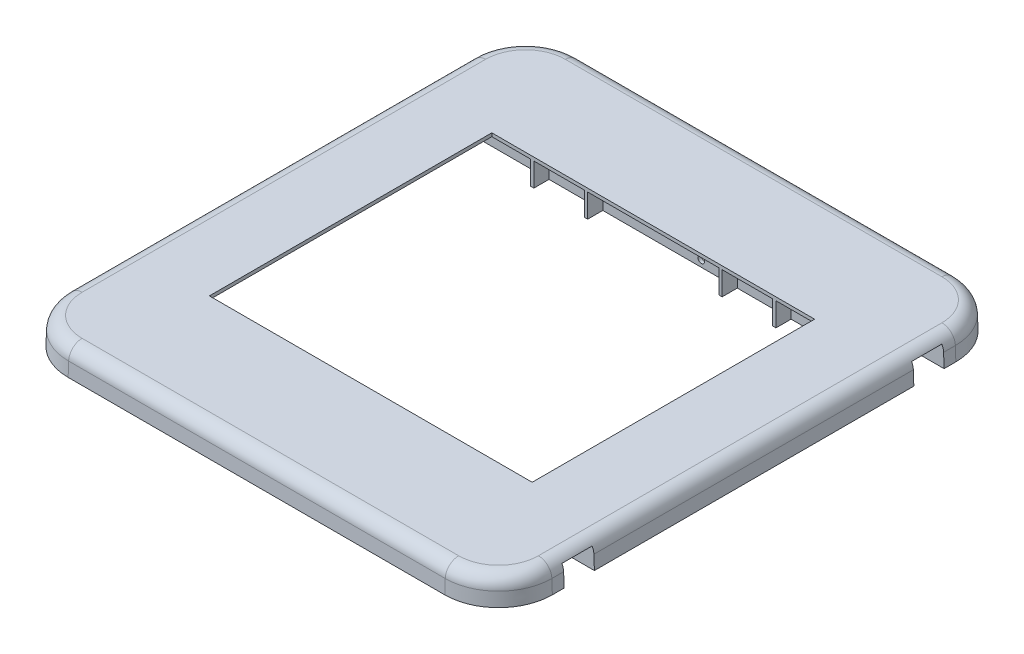
SolidWorks part; units mm, degrees
material "ABS PC"
ref_plane "Front Plane" through (0, 0, 0) normal (0, 0, 1) x (1, 0, 0)
ref_plane "Top Plane" through (0, 0, 0) normal (0, 1, 0) x (1, 0, 0)
ref_plane "Right Plane" through (0, 0, 0) normal (1, 0, 0) x (0, 0, -1)
sketch "Sketch1" plane through (0, 0, 0) normal (0, 1, 0) x (1, 0, 0)
  line L1 (-228.6, 0) -> (-256.2277, 0) construction
  line L2 (228.6, 0) -> (228.6, 190.5)
  line L3 (177.8, 241.3) -> (-177.8, 241.3)
  line L4 (-228.6, 0) -> (-228.6, 190.5)
  line L5 (-228.6, 0) -> (228.6, 0)
  arc A0 (-177.8, 241.3) -> (-228.6, 190.5) centre (-177.8, 190.5) ccw
  arc A1 (228.6, 190.5) -> (177.8, 241.3) centre (177.8, 190.5) ccw
  dimension "D3" = 50.8
  dimension "D1" = 457.2
  dimension "D2" = 482.6
extrude "Extrude1" add sketch "Sketch1" along normal blind 25.4
draft "Draft1" type of draft neutral plane draft angle 2 faces to draft 1 face at (228.6, 12.7, -95.25) neutral plane through (-177.8, 0, -190.5) neutral plane normal (0, -1, 0) reverse direction yes parameters "D1"=2
fillet "Fillet1" radius 12.7 5 edges at (-227.713, 25.4, -95.25) (-213.0938, 25.4, -225.7938) (0, 25.4, -240.413) (213.0938, 25.4, -225.7938) (227.713, 25.4, -95.25)
shell "Shell2" thickness 3.175 removed face at (0, 0, -147.4403) removed face at (0, 13.7024, 0)
sketch "Sketch3" plane through (0, 0, 0) normal (0, -1, 0) x (1, 0, 0)
  line L1 (-225.4231, -190.5) -> (-225.4231, 0) construction
  line L4 (-225.4231, -149.225) -> (215.4488, -149.225)
  line L5 (215.4488, 0) -> (215.4488, -190.5) construction
  line L6 (-228.6, -180.975) -> (215.4488, -180.975)
  line L7 (-228.6, -190.5) -> (-228.6, 0) construction
  line L8 (0, 0) -> (223.0829, 0) construction
  dimension "D1" = 298.45
  dimension "D2" = 361.95
rib "Rib1" sketch "Sketch3" sketch "Sketch3" thickness 3.175 extrusion direction normal to sketch draft on no parameters "D1"=3.175
sketch "Sketch4" plane through (0, 0, 0) normal (1, 0, 0) x (0, 0, -1)
  line L0 (150.8125, 19.05) -> (179.3875, 19.05)
  line L1 (150.8125, 19.05) -> (179.3875, 19.05) construction
  line L2 (150.8125, 0) -> (179.3875, 0) construction
  line L3 (150.8125, 22.225) -> (179.3875, 22.225) construction
  line L4 (150.8125, 13.0324) -> (150.8125, 0) construction
  line L5 (179.3875, 13.0324) -> (179.3875, 0) construction
  line L6 (150.8125, 0) -> (179.3875, 0)
  line L7 (150.8125, 22.225) -> (179.3875, 22.225) construction
  line L8 (150.8125, 0) -> (150.8125, 19.05)
  line L9 (179.3875, 0) -> (179.3875, 19.05)
  dimension "D1" = 3.175
extrude "Cut-Extrude2" cut sketch "Sketch4" along normal through all
sketch "Sketch6" plane through (0, 0, 0) normal (0, 0, 1) x (1, 0, 0)
  line L0 (228.141, 13.1432) -> (228.6, 0) construction
  line L1 (-225.4231, 0) -> (225.4231, 0) construction
  circle A1 centre (208.9354, 6.35) radius 3.175
  circle A3 centre (31.1354, 6.35) radius 3.175
  dimension "D2" = 6.35
  dimension "D3" = 177.8
  dimension "D4" = 19.431
  dimension "D1" = 6.35
extrude "Cut-Extrude3" cut sketch "Sketch6" against normal up to surface (207.9625 mm away) from offset 25.4
sketch "Sketch9" plane through (0, 19.05, 0) normal (0, -1, 0) x (1, 0, 0)
  line L0 (0, 0) -> (0, -59.2425) construction
  line L1 (63.5, -150.8125) -> (63.5, -179.3875)
  line L2 (-225.4231, -150.8125) -> (228.6, -150.8125) construction
  line L3 (-225.4231, -179.3875) -> (228.6, -179.3875) construction
  line L4 (-63.5, -150.8125) -> (-63.5, -179.3875)
  dimension "D1" = 127
rib "Rib4" sketch "Sketch9" sketch "Sketch9" thickness 3.175 extrusion direction normal to sketch draft on yes draft angle 2 parameters "D1"=3.175, "D3"=2
mirror "Mirror1" about plane through (-228.6, 25.4, 0) normal (0, 0, -1) of bodies 105 107
sketch "Sketch11" plane through (0, 0, 0) normal (0, -1, 0) x (1, 0, 0)
  line L0 (63.5, 147.6375) -> (63.5, -147.6375)
  line L5 (-225.4231, 147.6375) -> (225.4231, 147.6375) construction
  line L6 (-225.4231, -147.6375) -> (225.4231, -147.6375) construction
  line L7 (-63.5, 147.6375) -> (-63.5, -150.8125)
  line L8 (-225.4231, -150.8125) -> (228.6, -150.8125) construction
  line L9 (-63.5, -150.8125) -> (-63.5, -179.3875) construction
  line L10 (63.5, -150.8125) -> (63.5, -179.3875) construction
  line L11 (114.3, 147.6375) -> (114.3, -147.6375)
  line L12 (-114.3, 147.6375) -> (-114.3, -150.8125)
  dimension "D1" = 50.8
  dimension "D2" = 50.8
rib "Rib5" sketch "Sketch11" sketch "Sketch11" thickness 3.175 extrusion direction normal to sketch draft on no parameters "D1"=3.175
sketch "Sketch10" plane through (0, 25.4, 0) normal (0, 1, 0) x (-1, 0, 0)
  line L1 (152.4, 0) -> (-152.4, 0) construction
  line L2 (152.4, 133.35) -> (152.4, -133.35)
  line L3 (152.4, -133.35) -> (-152.4, -133.35)
  line L4 (-152.4, 133.35) -> (-152.4, -133.35)
  line L5 (152.4, 133.35) -> (-152.4, 133.35)
  dimension "D1" = 304.8
  dimension "D2" = 266.7
extrude "Cut-Extrude4" cut sketch "Sketch10" against normal through all
